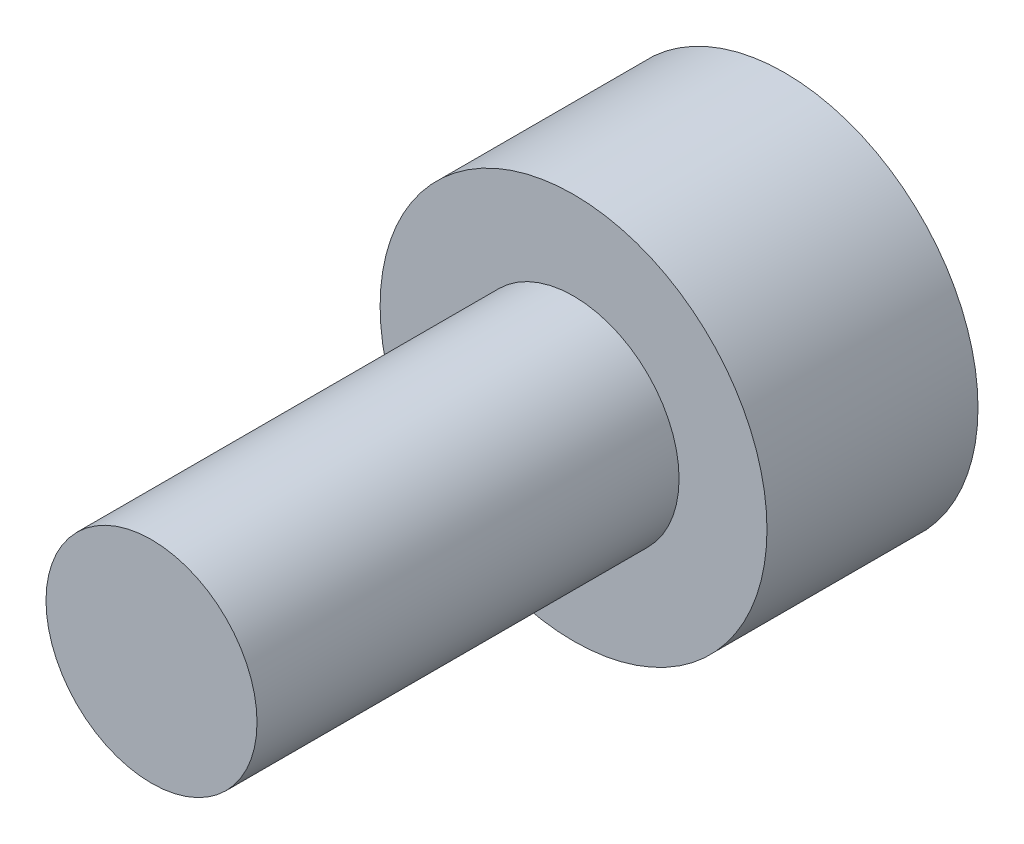
SolidWorks part; units mm, degrees
material "Stainless Steel (ferritic)"
ref_plane "Front Plane" through (0, 0, 0) normal (0, 0, 1) x (1, 0, 0)
ref_plane "Top Plane" through (0, 0, 0) normal (0, 1, 0) x (1, 0, 0)
ref_plane "Right Plane" through (0, 0, 0) normal (1, 0, 0) x (0, 0, -1)
sketch "Sketch1" plane through (0, 0, 0) normal (0, 0, 1) x (1, 0, 0)
  circle A0 centre (0, 0) radius 2.75
  circle A1 centre (0, 0) radius 1.5
  dimension "D1" = 5.5
  dimension "D2" = 3
extrude "Boss-Extrude1" add sketch "Sketch1" against normal blind 3 contours A0 A1 | A1 region at (-2.6722, 0, 0) region at (0, 0, 0)
extrude "Boss-Extrude2" add sketch "Sketch1<3>" along normal blind 6 contours A1 region at (0, 0, 0)
sketch "Sketch1<3>" plane through (0, 0, 0) normal (0, 0, 1) x (1, 0, 0) same geometry as "Sketch1"
